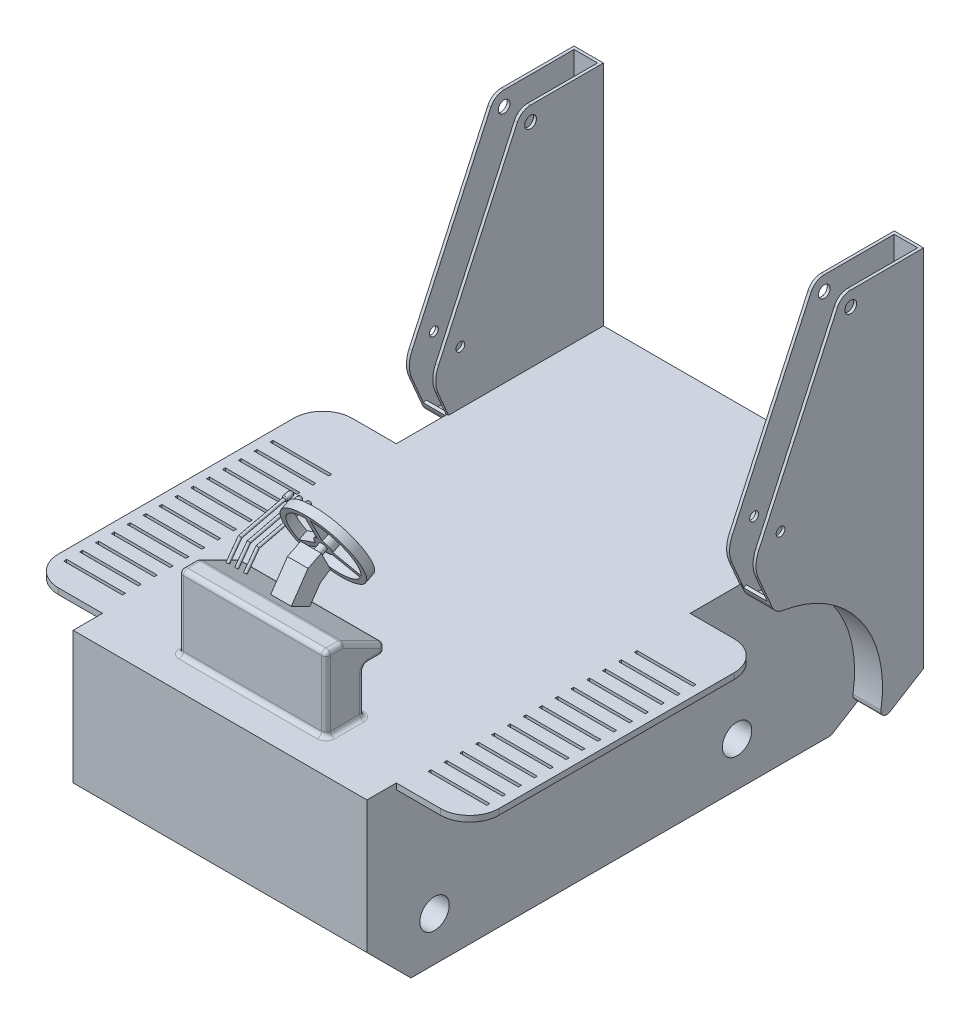
SolidWorks part; units mm, degrees
note: The reader was unsure of these and kept them because the rebuilt part matched: shared geometry of "Szkic2<4>".
ref_plane "Płaszczyzna przednia" through (0, 0, 0) normal (0, 0, 1) x (1, 0, 0)
ref_plane "Płaszczyzna górna" through (0, 0, 0) normal (0, 1, 0) x (1, 0, 0)
ref_plane "Płaszczyzna prawa" through (0, 0, 0) normal (1, 0, 0) x (0, 0, -1)
sketch "Szkic1" plane through (0, 0, 0) normal (1, 0, 0) x (0, 0, -1)
  line L0 (-778.3019, 600) -> (1021.6981, 600)
  line L1 (1021.6981, 600) -> (1021.6981, 135)
  line L2 (1021.6981, 135) -> (801.6981, 0)
  line L3 (801.6981, 0) -> (-628.3019, 0)
  line L4 (-628.3019, 0) -> (-778.3019, 150)
  line L5 (-778.3019, 150) -> (-778.3019, 600)
  circle A0 centre (-548.3019, 150) radius 50
  circle A1 centre (481.6981, 150) radius 50
  dimension "D8" = 100
  dimension "D1" = 1800
  dimension "D2" = 600
  dimension "D3" = 150
  dimension "D4" = 150
  dimension "D5" = 220
  dimension "D6" = 135
  dimension "D7" = 1030
  dimension "D9" = 150
  dimension "D10" = 540
extrude "Dodanie-wyciągnięcie1" add sketch "Szkic1" along normal mid plane 1000
sketch "Szkic2" plane through (500, 0, 0) normal (1, 0, 0) x (0, 0, -1)
  line L0 (1021.6981, 135) -> (1021.6981, 600)
  line L1 (1021.6981, 600) -> (1021.6981, 1375)
  line L2 (1021.6981, 1375) -> (773.7213, 1375)
  line L3 (728.3046, 1345.9122) -> (460.2856, 763.8338)
  line L4 (459.2046, 682.6174) -> (505.3762, 574.8835)
  line L5 (1021.6981, 135) -> (906.5123, 64.3178)
  line L6 (801.6981, 0) -> (1021.6981, 135) construction
  arc A0 (906.5123, 64.3178) -> (876.3209, 84.6326) centre (896.052, 81.3643) cw
  arc A1 (876.3209, 84.6326) -> (543.5962, 545.1818) centre (481.6981, 150) ccw
  circle A2 centre (481.6981, 150) radius 50 construction
  arc A3 (773.7213, 1375) -> (728.3046, 1345.9122) centre (773.7213, 1325) ccw
  arc A4 (460.2856, 763.8338) -> (459.2046, 682.6174) centre (551.1191, 722.0093) ccw
  arc A5 (543.5962, 545.1818) -> (505.3762, 574.8835) centre (551.3335, 594.5795) cw
  point P18 (741.6981, 1375)
  point P21 (441.6981, 723.4658)
  point P24 (516.6981, 548.4658)
  dimension "D5" = 400
  dimension "D6" = 20
  dimension "D8" = 50
  dimension "D9" = 100
  dimension "D10" = 50
  dimension "D1" = 1240
  dimension "D2" = 280
  dimension "D3" = 75
  dimension "D4" = 175
  dimension "D7" = 35
extrude "Dodanie-wyciągnięcie2" add sketch "Szkic2" along normal mid plane 10 separate body
sketch "Szkic3" plane through (505, 0, 0) normal (1, 0, 0) x (0, 0, -1)
  line L0 (1021.6981, 135) -> (1021.6981, 1375) construction
  line L1 (906.5123, 64.3178) -> (1021.6981, 135) construction
  line L2 (1021.6981, 135) -> (1021.6981, 1375)
  line L3 (906.5123, 64.3178) -> (1021.6981, 135)
  line L4 (505.3762, 574.8835) -> (499.3263, 589)
  line L5 (459.2046, 682.6174) -> (505.3762, 574.8835) construction
  line L6 (514.5677, 578.8227) -> (508.5178, 592.9392)
  line L7 (901.2822, 72.841) -> (1011.6981, 140.5963)
  line L8 (1011.6981, 140.5963) -> (1011.6981, 1375)
  line L9 (505.3762, 574.8835) -> (498.794, 590.242) construction
  line L10 (514.5677, 578.8227) -> (507.9855, 594.1812) construction
  line L11 (499.3263, 589) -> (508.5178, 592.9392)
  line L12 (1011.6981, 1375) -> (1021.6981, 1375)
  line L13 (1021.6981, 600) -> (-778.3019, 600) construction
  arc A0 (876.3209, 84.6326) -> (906.5123, 64.3178) centre (896.052, 81.3643) ccw construction
  arc A1 (876.3209, 84.6326) -> (543.5962, 545.1818) centre (481.6981, 150) ccw construction
  arc A2 (876.3209, 84.6326) -> (543.5962, 545.1818) centre (481.6981, 150) ccw
  arc A3 (876.3209, 84.6326) -> (906.5123, 64.3178) centre (896.052, 81.3643) ccw
  arc A4 (505.3762, 574.8835) -> (543.5962, 545.1818) centre (551.3335, 594.5795) ccw construction
  arc A5 (505.3762, 574.8835) -> (543.5962, 545.1818) centre (551.3335, 594.5795) ccw
  arc A6 (514.5677, 578.8227) -> (545.1437, 555.0613) centre (551.3335, 594.5795) ccw
  arc A7 (886.1864, 82.9984) -> (545.1437, 555.0613) centre (481.6981, 150) ccw
  arc A8 (886.1864, 82.9984) -> (901.2822, 72.841) centre (896.052, 81.3643) ccw
  dimension "D2" = 11
  dimension "D1" = 10
extrude "Dodanie-wyciągnięcie3" add sketch "Szkic3" along normal blind 80
extrude "Dodanie-wyciągnięcie5" add sketch "Szkic2<4>" along normal mid plane 10 from offset 90
sketch "Szkic2<4>" plane through (500, 0, 0) normal (1, 0, 0) x (0, 0, -1) same geometry as "Szkic2"
mirror "Lustro1" about plane through (0, 0, 0) normal (1, 0, 0) of bodies 105
sketch "Szkic5" plane through (595, 0, 0) normal (1, 0, 0) x (0, 0, -1)
  line L0 (728.3046, 1345.9122) -> (460.2856, 763.8338) construction
  circle A0 centre (773.7213, 1325) radius 20
  circle A1 centre (534.7095, 782.0093) radius 15
  arc A2 (460.2856, 763.8338) -> (459.2046, 682.6174) centre (551.1191, 722.0093) ccw construction
  point P7 (0, 0)
  point P8 (0, 0)
  dimension "D1" = 30
  dimension "D4" = 40
  dimension "D2" = 60
  dimension "D3" = 60
extrude "Wytnij-wyciągnięcie1" cut sketch "Szkic5" against normal through all
sketch "Szkic6" plane through (0, 600, 0) normal (0, 1, 0) x (1, 0, 0)
  line L0 (0, 0) -> (0, -778.3019) construction
  line L1 (500, -778.3019) -> (-500, -778.3019) construction
  line L2 (500, 1021.6981) -> (500, -778.3019) construction
  line L3 (500, 321.6981) -> (650, 321.6981)
  line L4 (500, 321.6981) -> (500, -678.3019)
  line L5 (500, -678.3019) -> (650, -678.3019)
  line L6 (750, 221.6981) -> (750, -578.3019)
  line L7 (-750, 221.6981) -> (-750, -578.3019)
  line L8 (-500, -678.3019) -> (-650, -678.3019)
  line L9 (-500, 321.6981) -> (-500, -678.3019)
  line L10 (-500, 321.6981) -> (-650, 321.6981)
  arc A0 (650, -678.3019) -> (750, -578.3019) centre (650, -578.3019) ccw
  arc A1 (650, 321.6981) -> (750, 221.6981) centre (650, 221.6981) cw
  arc A2 (-650, 321.6981) -> (-750, 221.6981) centre (-650, 221.6981) ccw
  arc A3 (-650, -678.3019) -> (-750, -578.3019) centre (-650, -578.3019) cw
  point P14 (750, -678.3019)
  point P17 (750, 321.6981)
  point P26 (-750, 321.6981)
  point P27 (-750, -678.3019)
  dimension "D4" = 100
  dimension "D1" = 1000
  dimension "D2" = 250
  dimension "D3" = 100
extrude "Dodanie-wyciągnięcie6" add sketch "Szkic6" against normal blind 20
sketch "Szkic7" plane through (0, 600, 0) normal (0, 1, 0) x (1, 0, 0)
  line L0 (750, -578.3019) -> (750, 221.6981) construction
  line L1 (520, 121.6981) -> (720, 121.6981)
  line L2 (520, 121.6981) -> (520, 111.6981)
  line L3 (520, 111.6981) -> (720, 111.6981)
  line L4 (720, 121.6981) -> (720, 111.6981)
  line L5 (650, 321.6981) -> (500, 321.6981) construction
  line L6 (0, 0) -> (0, -377.7051) construction
  line L7 (-720, 121.6981) -> (-720, 111.6981)
  line L8 (-520, 111.6981) -> (-720, 111.6981)
  line L9 (-520, 121.6981) -> (-520, 111.6981)
  line L10 (-520, 121.6981) -> (-720, 121.6981)
  dimension "D1" = 200
  dimension "D2" = 10
  dimension "D3" = 30
  dimension "D4" = 200
extrude "Wytnij-wyciągnięcie2" cut sketch "Szkic7" against normal through all
pattern_linear "Szyk liniowy1" count 14 spacing 54 along (0, 0, 1) of "Wytnij-wyciągnięcie2"
sketch "Szkic9" plane through (0, 600, 0) normal (0, 1, 0) x (1, 0, 0)
  line L0 (0, 0) -> (0, -778.3019) construction
  line L1 (500, -778.3019) -> (-500, -778.3019) construction
  line L2 (-250, -468.0036) -> (250, -668.0036) construction
  line L3 (-250, -468.0036) -> (250, -468.0036)
  line L4 (-250, -468.0036) -> (-250, -668.0036)
  line L5 (-250, -668.0036) -> (250, -668.0036)
  line L6 (250, -468.0036) -> (250, -668.0036)
  line L7 (250, -468.0036) -> (-250, -668.0036) construction
  point P9 (0, -568.0036)
  dimension "D1" = 500
  dimension "D2" = 200
  dimension "D3" = 110.2983
extrude "Dodanie-wyciągnięcie7" add sketch "Szkic9" along normal blind 253
sketch "Szkic10" plane through (250, 0, 0) normal (1, 0, 0) x (0, 0, -1)
  line L0 (-468.0036, 853) -> (-608.0036, 853)
  line L1 (-668.0036, 853) -> (-468.0036, 853) construction
  line L2 (-608.0036, 853) -> (-468.0036, 783)
  line L3 (-468.0036, 853) -> (-468.0036, 600) construction
  line L4 (-468.0036, 783) -> (-468.0036, 853)
  line L5 (-538.0036, 600) -> (-538.0036, 750)
  line L6 (-578.3019, 600) -> (221.6981, 600) construction
  line L7 (-538.0036, 750) -> (-468.0036, 750)
  line L8 (-538.0036, 600) -> (-468.0036, 600)
  line L9 (-468.0036, 600) -> (-468.0036, 750)
  dimension "D1" = 70
  dimension "D2" = 150
  dimension "D3" = 70
  dimension "D4" = 140
extrude "Wytnij-wyciągnięcie3" cut sketch "Szkic10" against normal through all
fillet "Zaokrąglenie2" radius 15 21 edges at (250, 750, 503.0036) (250, 600, 603.0036) (0, 750, 468.0036) (250, 766.5, 468.0036) (0, 600, 538.0036) (250, 675, 538.0036) (0, 750, 538.0036) (0, 783, 468.0036) (250, 818, 538.0036) (250, 853, 638.0036) (0, 853, 608.0036) (0, 853, 668.0036) (250, 726.5, 668.0036) (0, 600, 668.0036) (-250, 726.5, 668.0036) (-250, 600, 603.0036) (-250, 675, 538.0036) (-250, 750, 503.0036) (-250, 766.5, 468.0036) (-250, 818, 538.0036) (-250, 853, 638.0036)
ref_plane "Płaszczyzna2" through (-220, 0, 0) normal (-1, 0, 0) x (0, 0, 1)
sketch "Szkic11" plane through (-220, 0, 0) normal (-1, 0, 0) x (0, 0, 1)
  line L0 (531.5446, 814.7705) -> (489.8432, 870.9932)
  line L1 (476.2954, 787.1459) -> (604.8364, 851.4164) construction
  line L2 (489.8432, 870.9932) -> (339.8432, 906.8249)
  point P4 (0, 0)
  dimension "D1" = 140
  dimension "D2" = 100
  dimension "D3" = 150
  dimension "D4" = 70
  dimension "D5" = 80
ref_plane "Płaszczyzna3" through (-220, 906.8249, 339.8432) normal (0, 0.2323, -0.9726) x (-1, 0, 0)
sketch "Szkic12" plane through (-220, 906.8249, 339.8432) normal (0, 0.2323, -0.9726) x (-1, 0, 0)
  circle A0 centre (0.073, 0.1941) radius 5
  dimension "D1" = 10
sweep "Wyciągnięcie po ścieżce1" add profiles "Szkic12" path "Szkic11"
sketch "Szkic13" plane through (0, -27.8462, 116.5705) normal (0, 0.2323, -0.9726) x (-1, 0, 0)
  circle A0 centre (220.073, 961.1628) radius 8.5
  dimension "D1" = 17
extrude "Dodanie-wyciągnięcie8" add sketch "Szkic13" along normal blind 30
fillet "Zaokrąglenie3" radius 8.5 1 edges at (-220.073, 922.2514, 312.6841)
fillet "Zaokrąglenie4" radius 3.5 1 edges at (-220.073, 915.2811, 341.8632)
pattern_linear "Szyk liniowy2" count 3 spacing 30 along (1, 0, 0) of bodies 115
sketch "Szkic15" plane through (0, 0, 0) normal (1, 0, 0) x (0, 0, -1)
  line L0 (-570.8364, 834.4164) -> (-513.7628, 917.7447)
  line L1 (-604.8364, 851.4164) -> (-476.2954, 787.1459) construction
  line L2 (-513.7628, 917.7447) -> (-469.0519, 940.1263)
  line L3 (-469.0519, 940.1263) -> (-437.7177, 877.531)
  line L4 (-437.7177, 877.531) -> (-472.5429, 854.0513)
  line L5 (-472.5429, 854.0513) -> (-507.6353, 802.8158)
  line L6 (-570.8364, 834.4164) -> (-507.6353, 802.8158)
  point P10 (-455.1303, 865.7912)
  dimension "D1" = 101
  dimension "D2" = 151
  dimension "D3" = 50
  dimension "D4" = 70
  dimension "D5" = 34
  dimension "D6" = 70
extrude "Dodanie-wyciągnięcie9" add sketch "Szkic15" along normal mid plane 70
sketch "Szkic16" plane through (0, 0.6245, -1.2476) normal (0, 0.4476, -0.8942) x (-1, 0, 0)
  line L0 (-35, 1050.6404) -> (35, 1050.6404) construction
  line L1 (35, 980.6404) -> (35, 1050.6404) construction
  circle A0 centre (0, 1015.6404) radius 12.5
  dimension "D1" = 25
  dimension "D2" = 35
  dimension "D3" = 35
extrude "Dodanie-wyciągnięcie10" add sketch "Szkic16" along normal blind 30
sketch "Szkic17" plane through (0, 14.0534, -28.0741) normal (0, 0.4476, -0.8942) x (-1, 0, 0)
  line L2 (-9, 1132.2937) -> (-9, 1044.2585)
  line L3 (9, 1132.2937) -> (9, 1044.2585)
  line L4 (105.5495, 965.1597) -> (29.297, 1009.1841)
  line L5 (96.5572, 949.5668) -> (20.3282, 993.5776)
  line L6 (-96.5572, 949.5668) -> (-20.3282, 993.5776)
  line L7 (-105.5534, 965.1575) -> (-29.297, 1009.1841)
  circle A0 centre (0, 1015.6404) radius 135
  arc A1 (-96.5572, 949.5668) -> (96.5572, 949.5668) centre (0, 1015.6404) ccw
  arc A2 (-9, 1044.2585) -> (-29.297, 1009.1841) centre (0, 1015.6404) ccw
  arc A4 (-20.3282, 993.5776) -> (20.3282, 993.5776) centre (0, 1015.6404) ccw
  arc A5 (29.297, 1009.1841) -> (9, 1044.2585) centre (0, 1015.6404) ccw
  arc A6 (105.5495, 965.1597) -> (9, 1132.2937) centre (0, 1015.6404) ccw
  arc A7 (-9, 1132.2937) -> (-105.5495, 965.1597) centre (0, 1015.6404) ccw
  point P24 (0, 1015.7064)
  dimension "D1" = 18
  dimension "D2" = 270
  dimension "D3" = 60
  dimension "D4" = 18
  dimension "D5" = 3
extrude "Dodanie-wyciągnięcie11" add sketch "Szkic17" along normal blind 30 separate body
